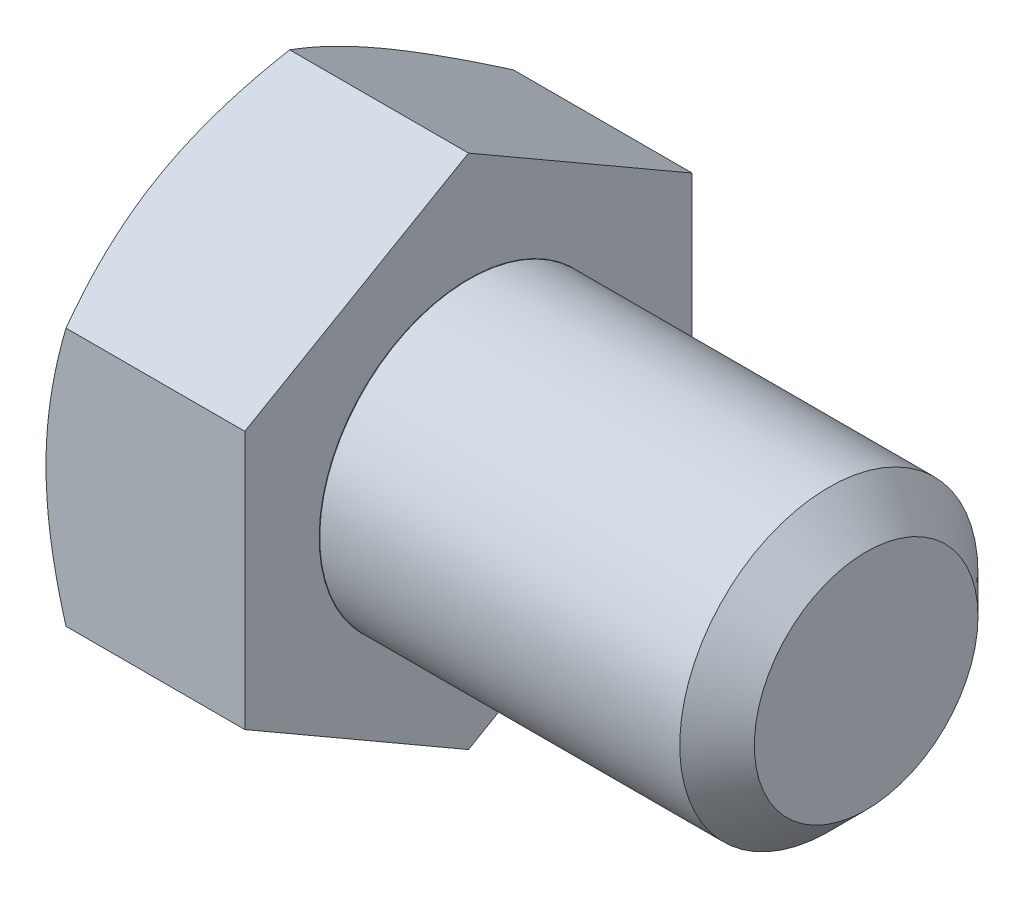
SolidWorks part; units mm, degrees
ref_plane "Front Plane" through (0, 0, 0) normal (0, 0, 1) x (1, 0, 0)
ref_plane "Top Plane" through (0, 0, 0) normal (0, 1, 0) x (1, 0, 0)
ref_plane "Right Plane" through (0, 0, 0) normal (1, 0, 0) x (0, 0, -1)
sketch "Sketch1" plane through (0, 0, 0) normal (0, 0, 1) x (1, 0, 0)
  line L0 (-9.525, 0) -> (9.525, 0) construction
  line L1 (9.525, 4.7625) -> (9.525, -4.7625) construction
  line L2 (-3.175, 7.1437) -> (-3.175, -7.1437) construction
  line L3 (-9.525, 7.1437) -> (-9.525, -7.1437) construction
  line L4 (-3.429, 4.7687) -> (-3.175, 4.7687) construction
  line L5 (-3.175, 4.7687) -> (5.0847, 0) construction
  line L6 (-3.429, 4.7687) -> (-3.429, 0) construction
  line L7 (-3.175, 0) -> (-3.175, 4.7687) construction
  point P9 (-3.175, 0)
  point P10 (3.9688, -4.7625)
  dimension "Screw Dia" = 9.525
  dimension "Hex" = 14.2875
  dimension "Head Ht" = 6.35
  dimension "Screw Length" = 12.7
  dimension "D1" = 5.5562
  dimension "D2" = 30
  dimension "D3" = 0.254
  dimension "MinThread" = 12.7
  dimension "D4" = 0.0124
ref_plane "Plane2" through (9.525, 0, 0) normal (1, 0, 0) x (0, 0, -1)
sketch "Sketch5" plane through (9.525, 0, 0) normal (1, 0, 0) x (0, 0, -1)
  circle A0 centre (0, 0) radius 4.7625
extrude "Boss-Extrude3" add sketch "Sketch5" against normal up to vertex (12.7 mm away) up to point (-3.175, 0, 0)
sketch "Sketch9" plane through (9.525, 0, 0) normal (1, 0, 0) x (0, 0, -1)
  circle A1 centre (0, 0) radius 4.7625
  circle A2 centre (0, 0) radius 4.7625
  dimension "D1" = 0
chamfer "Chamfer1" distance 1.1906 angle 45 1 edges at (9.525, 0, -4.7625)
sketch "Sketch6" plane through (-3.175, 0, 0) normal (-1, 0, 0) x (0, 0, 1)
  line L0 (0, 7.1437) -> (0, -7.1437) construction
  line L1 (7.1437, 4.1244) -> (0, 8.2489)
  line L2 (0, 8.2489) -> (-7.1438, 4.1244)
  line L3 (-7.1438, 4.1244) -> (-7.1438, -4.1244)
  line L4 (-7.1438, -4.1244) -> (0, -8.2489)
  line L5 (0, -8.2489) -> (7.1438, -4.1244)
  line L6 (7.1438, -4.1244) -> (7.1437, 4.1244)
  circle A0 centre (0, 0) radius 7.1438 construction
extrude "Boss-Extrude4" add sketch "Sketch6" along normal up to vertex (6.35 mm away) separate body up to point (-9.525, -7.1437, 0)
sketch "Sketch7" plane through (-9.525, 0, 0) normal (-1, 0, 0) x (0, 0, 1)
  circle A0 centre (0, 0) radius 7.1438 construction
  circle A1 centre (0, 0) radius 7.1438
sketch "Sketch8" plane through (-9.525, 0, 0) normal (-1, 0, 0) x (0, 0, 1)
  circle A0 centre (0, 0) radius 7.1438 construction
  circle A1 centre (0, 0) radius 7.1438
extrude "Cut-Extrude3" cut sketch "Sketch8" against normal through all draft 60 flip side to cut
sketch "Sketch12" plane through (-9.525, 0, 0) normal (-1, 0, 0) x (0, 0, 1)
  line L0 (0, 5.5007) -> (0, 3.0718) construction
  line L1 (0.2143, 5.5007) -> (0.2143, 3.0718)
  line L2 (-0.2143, 5.5007) -> (-0.2143, 3.0718)
  line L3 (0, 4.7625) -> (0, -4.7625) construction
  arc A0 (0.2143, 5.5007) -> (-0.2143, 5.5007) centre (0, 5.5007) ccw
  arc A1 (-0.2143, 3.0718) -> (0.2143, 3.0718) centre (0, 3.0718) ccw
  circle A3 centre (0, 0) radius 2.8575 construction
  circle A4 centre (0, 0) radius 5.715 construction
  point P2 (0, 4.2862)
  dimension "D1" = 5.715
  dimension "D3" = 11.43
  dimension "D2" = 0.4286
extrude "Cut-Extrude4" [suppressed] cut sketch "Sketch12" against normal blind 0.254
pattern_circular "CirPattern1" [suppressed] count 6 over 360 of bodies 104
curve "Helix/Spiral1" [suppressed] pitch 1.5875 height 14.2875 turns 9 parameters "Pitch"=1.5875
sketch "Sketch10" plane through (0, 0, 0) normal (0, 0, 1) x (1, 0, 0)
  line L0 (9.525, 4.7625) -> (10.1203, 3.7314)
  line L1 (10.1203, 3.7314) -> (10.3188, 3.7314)
  line L2 (10.3188, 3.7314) -> (10.9141, 4.7625)
  line L3 (9.525, 4.7625) -> (10.9141, 4.7625)
  line L4 (10.2195, 4.7625) -> (10.2195, 3.7314) construction
  line L5 (9.8227, 4.2469) -> (10.6164, 4.2469) construction
  dimension "D1" = 60
  dimension "D2" = 0.1984
  dimension "D3" = 0.7937
sweep "Cut-Sweep1" [suppressed] cut profiles "Sketch10" path "Helix/Spiral1"
sketch "Sketch13" plane through (0, 0, 0) normal (0, 0, 1) x (1, 0, 0)
  line L0 (-9.525, 0) -> (9.525, 0) construction
  line L1 (-3.175, 4.7687) -> (5.0847, 0) construction
  line L2 (-3.429, 4.7687) -> (-3.175, 4.7687) construction
  line L3 (-3.429, 4.7687) -> (-3.429, 0) construction
  line L4 (-3.429, 0) -> (5.0847, 0)
  line L5 (-3.175, 4.7687) -> (5.0847, 0)
  line L6 (-3.429, 4.7687) -> (-3.175, 4.7687)
  line L7 (-3.429, 4.7687) -> (-3.429, 0)
revolve "Revolve7" add sketch "Sketch13" angle 360 about L4
ref_axis "Center Axis 1" through (-3.1642, 0, 0) along (1, 0, 0)
ref_plane "Contact Plane 1" through (-3.175, 0, 0) normal (1, 0, 0) x (0, 0, -1)
equation "\"D2@Sketch10\" = \"Pitch@Helix/Spiral1\"*.125"
equation "\"D3@Sketch10\" = \"Pitch@Helix/Spiral1\"*.5"
equation "\"D3@Helix/Spiral1\" = \"Screw Length@Sketch1\" + \"Pitch@Helix/Spiral1\""
equation "\"D1@Chamfer1\" = \"Pitch@Helix/Spiral1\"*.75"
equation "\"D1@Sketch12\" = \"Hex@Sketch1\"*.4"
equation "\"D3@Sketch12\" = \"Hex@Sketch1\"*.8"
equation "\"D2@Sketch12\" = \"Hex@Sketch1\"*.03"
equation "\"D1@Sketch1\" = \"Pitch@Helix/Spiral1\"*3.5"
